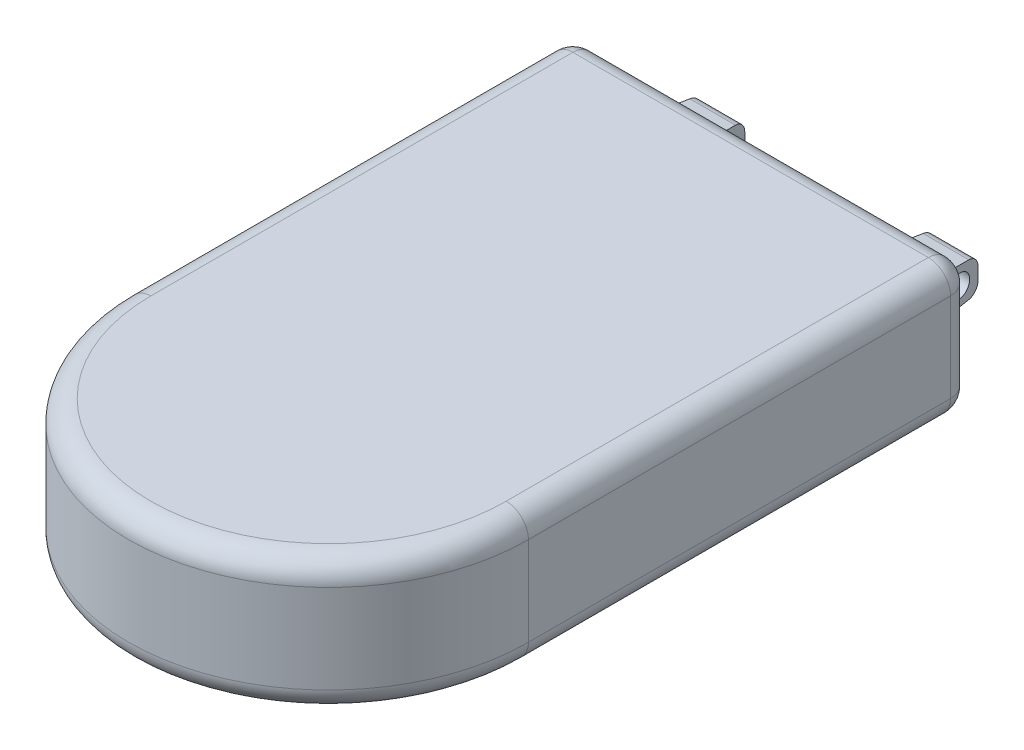
SolidWorks part; units mm, degrees
ref_plane "Front Plane" through (0, 0, 0) normal (0, 0, 1) x (1, 0, 0)
ref_plane "Top Plane" through (0, 0, 0) normal (0, 1, 0) x (1, 0, 0)
ref_plane "Right Plane" through (0, 0, 0) normal (1, 0, 0) x (0, 0, -1)
sketch "Sketch1" plane through (0, 0, 0) normal (0, 1, 0) x (1, 0, 0)
  line L0 (-228.6, 0) -> (-228.6, 1524)
  line L1 (-228.6, 0) -> (228.6, 0)
  line L2 (228.6, 0) -> (228.6, 1524)
  line L3 (-228.6, 1524) -> (228.6, 1524)
  line L4 (-228.6, -342.0511) -> (228.6, -342.0511)
  line L5 (-228.6, -342.0511) -> (-228.6, -850.0511)
  line L6 (228.6, -342.0511) -> (228.6, -850.0511)
  line L7 (0, -850.0511) -> (0, 1524)
  circle A0 centre (0, 1524) radius 228.6
  circle A1 centre (0, -850.0511) radius 228.6
  point P6 (0, 0)
  point P9 (0, 1524)
  dimension "D1" = 1524
  dimension "D2" = 457.2
  dimension "D3" = 508
extrude "Boss-Extrude1" add sketch "Sketch1" along normal blind 152.4 contours A1 | A1 L6 L4 L7 | A1 L7 L4 L5 region at (123.7451, 0, 510.243) region at (-123.7451, 0, 510.243) region at (157.0726, 0, 692.9785)
fillet "Fillet1" radius 25.4 10 edges at (0, 0, 1078.6511) (228.6, 152.4, 596.0511) (0, 152.4, 1078.6511) (228.6, 0, 596.0511) (-228.6, 0, 596.0511) (-228.6, 76.2, 342.0511) (228.6, 76.2, 342.0511) (0, 0, 342.0511) (0, 152.4, 342.0511) (-228.6, 152.4, 596.0511)
sketch "Sketch3" plane through (0, 0, 0) normal (0, -1, 0) x (1, 0, 0)
  line L0 (0, 367.4511) -> (0, 491.6161)
  line L1 (-203.2, 367.4511) -> (203.2, 367.4511) construction
  line L2 (-133.35, 367.4511) -> (133.35, 367.4511)
  line L5 (114.3, 367.4511) -> (114.3, 850.0511)
  line L6 (-114.3, 850.0511) -> (-114.3, 367.4511)
  line L7 (133.35, 367.4511) -> (133.35, 850.0511)
  line L8 (-133.35, 850.0511) -> (-133.35, 367.4511)
  line L9 (133.35, 367.4511) -> (133.35, 850.0511)
  line L10 (-133.35, 850.0511) -> (-133.35, 367.4511)
  arc A1 (114.3, 850.0511) -> (-114.3, 850.0511) centre (0, 850.0511) ccw
  arc A2 (133.35, 850.0511) -> (-133.35, 850.0511) centre (0, 850.0511) ccw
  arc A3 (133.35, 850.0511) -> (-133.35, 850.0511) centre (0, 850.0511) ccw
  point P7 (0, 367.4511)
  line M11 (-203.2, 367.4511) -> (203.2, 367.4511)
  dimension "D1" = 69.85
  dimension "D2" = 19.05
extrude "Boss-Extrude2" add sketch "Sketch3" along normal blind 50.8 contours L9 A3 L10 L6 A1 L5 L2 M11 region at (-126.6379, 0, 608.7511)
sketch "Sketch4" plane through (0, 0, 0) normal (0, -1, 0) x (1, 0, 0)
  line L3 (-114.3, 850.0511) -> (-114.3, 367.4511)
  line L4 (-114.3, 367.4511) -> (114.3, 367.4511)
  line L5 (114.3, 367.4511) -> (114.3, 850.0511)
  line L6 (-114.3, 850.0511) -> (-114.3, 367.4511)
  line L7 (-114.3, 367.4511) -> (114.3, 367.4511)
  line L8 (114.3, 367.4511) -> (114.3, 850.0511)
  arc A1 (114.3, 850.0511) -> (-114.3, 850.0511) centre (0, 850.0511) ccw
  arc A2 (114.3, 850.0511) -> (-114.3, 850.0511) centre (0, 850.0511) ccw
  dimension "D1" = 0
extrude "Boss-Extrude3" add sketch "Sketch4" along normal blind 25.4
fillet "Fillet2" radius 25.4 3 edges at (123.825, -50.8, 367.4511) (-123.825, -50.8, 367.4511) (0, -25.4, 367.4511)
sketch "Sketch5" plane through (0, 0, 342.0511) normal (0, 0, -1) x (-1, 0, 0)
  line L0 (0, 127) -> (0, -28.8848)
  line L1 (-203.2, 63.5) -> (203.2, 63.5)
  line L2 (0, 127) -> (-203.2, 127)
  line L3 (-101.6, 127) -> (-101.6, 0)
  line L4 (-165.1, 127) -> (-165.1, 0)
  line L5 (101.6, 127) -> (101.6, 0)
  line L6 (165.1, 127) -> (165.1, 0)
  line L7 (-165.1, 88.9) -> (-101.6, 88.9)
  line L8 (165.1, 88.9) -> (101.6, 88.9)
  line L9 (165.1, 38.1) -> (101.6, 38.1)
  line L10 (-165.1, 38.1) -> (-101.6, 38.1)
  line L11 (0, 127) -> (0, -82.5349)
  line L12 (203.2, 127) -> (-203.2, 127) construction
  point P17 (165.1, 63.5)
  point P20 (101.6, 63.5)
  point P21 (-101.6, 63.5)
  point P24 (-165.1, 63.5)
  dimension "D1" = 63.5
  dimension "D2" = 25.4
extrude "Boss-Extrude4" add sketch "Sketch5" along normal blind 76.2 draft 5 contours L4 L10 L3 L1 | L7 L4 L1 L3 | L9 L6 L1 L5 | L6 L8 L5 L1 region at (-133.35, 76.2, 342.0511) region at (-133.35, 50.8, 342.0511) region at (133.35, 50.8, 342.0511) region at (133.35, 76.2, 342.0511)
fillet "Fillet3" radius 12.7 4 edges at (-133.35, 44.7666, 265.8511) (133.35, 44.7666, 265.8511) (133.35, 82.2334, 265.8511) (-133.35, 82.2334, 265.8511)
sketch "Sketch6" plane through (-134.1476, 0, -11.7364) normal (-0.9962, 0, -0.0872) x (-0.0872, 0, 0.9962)
  line L0 (251.0311, 63.5) -> (301.8311, 63.5)
  line L1 (251.0311, 70.596) -> (251.0311, 56.404) construction
  circle A0 centre (301.8311, 63.5) radius 12.7
  point P6 (251.0311, 63.5)
  dimension "D1" = 25.4
  dimension "D2" = 50.8
sketch "Sketch7" plane through (-228.6, 0, 0) normal (-1, 0, 0) x (0, 0, 1)
  ellipse E0 centre (288.9461, 63.5) end of major axis (288.9461, 76.2) minor radius 12.6517 construction
  ellipse E1 centre (288.9461, 63.5) end of major axis (288.9461, 76.2) minor radius 12.6517
extrude "Cut-Extrude2" cut sketch "Sketch7" against normal through all
scale "Scale1" scale about centroid uniform scaling yes scale factor 0.75
